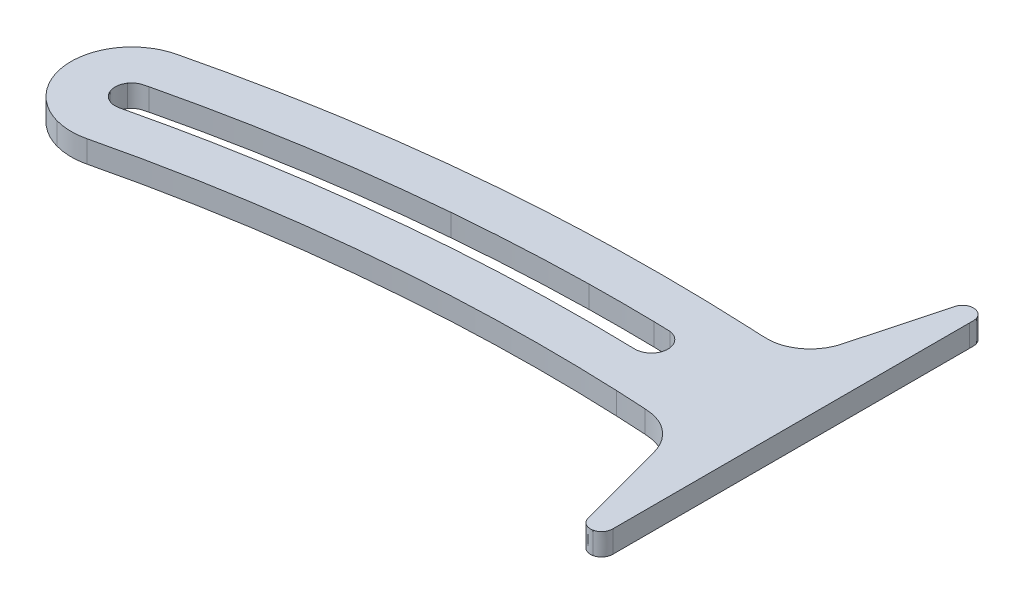
SolidWorks part; units mm, degrees
ref_plane "Front Plane" through (0, 0, 0) normal (0, 0, 1) x (1, 0, 0)
ref_plane "Top Plane" through (0, 0, 0) normal (0, 1, 0) x (1, 0, 0)
ref_plane "Right Plane" through (0, 0, 0) normal (1, 0, 0) x (0, 0, -1)
sketch "Imported Profile" plane through (0, 0, 0) normal (0, 1, 0) x (1, 0, 0)
  spline S0 degree 3 poles (12.8991, 25.236) (15.9171, 24.4093) (18.7007, 24.3473) (21.7531, 25.0501) knots 0 0 0 0 1 1 1 1
  spline S1 degree 3 poles (21.7531, 25.0501) (67.2422, 35.9573) (114.0335, 40.4773) (160.7696, 38.4929) knots 0 0 0 0 1 1 1 1
  spline S2 degree 3 poles (160.7696, 38.4929) (163.6635, 38.3689) (166.5574, 38.2174) (169.4444, 38.0449) knots 0 0 0 0 1 1 1 1
  spline S3 degree 3 poles (169.4444, 38.0449) (172.5863, 37.8589) (175.1081, 37.0734) (177.5541, 34.9719) knots 0 0 0 0 1 1 1 1
  spline S4 degree 3 poles (177.5541, 34.9719) (178.7254, 33.9728) (179.6419, 32.8428) (180.3929, 31.4993) knots 0 0 0 0 1 1 1 1
  spline S5 degree 3 poles (180.3929, 31.4993) (181.1026, 30.2177) (181.4953, 28.8603) (181.8674, 27.4685) knots 0 0 0 0 1 1 1 1
  spline S6 degree 3 poles (181.8674, 27.4685) (182.6184, 24.6642) (183.3694, 21.8599) (184.1205, 19.0625) knots 0 0 0 0 1 1 1 1
  spline S7 degree 3 poles (184.1205, 19.0625) (184.8715, 16.2582) (185.6225, 13.4539) (186.3735, 10.6495) knots 0 0 0 0 1 1 1 1
  spline S8 degree 3 poles (186.3735, 10.6495) (186.7457, 9.2508) (187.1246, 7.8521) (187.4967, 6.4465) knots 0 0 0 0 1 1 1 1
  spline S9 degree 3 poles (187.4967, 6.4465) (187.6827, 5.7506) (187.8756, 5.0478) (188.0617, 4.345) knots 0 0 0 0 1 1 1 1
  spline S10 degree 3 poles (188.0617, 4.345) (188.2477, 3.6491) (188.3786, 2.9463) (188.6335, 2.2642) knots 0 0 0 0 1 1 1 1
  spline S11 degree 3 poles (188.6335, 2.2642) (189.1847, 0.8172) (190.7006, -0.0165) (192.2233, 0.2798) knots 0 0 0 0 1 1 1 1
  spline S12 degree 3 poles (192.2233, 0.2798) (193.7874, 0.5968) (194.7796, 1.9335) (194.7796, 3.4975) knots 0 0 0 0 1 1 1 1
  spline S13 degree 3 poles (194.7796, 3.4975) (194.7796, 6.3983) (194.7796, 9.2991) (194.7796, 12.1998) knots 0 0 0 0 1 1 1 1
  spline S14 degree 3 poles (194.7796, 12.1998) (194.7796, 35.5507) (194.7796, 58.9084) (194.7796, 82.2593) knots 0 0 0 0 1 1 1 1
  spline S15 degree 3 poles (194.7796, 82.2593) (194.7796, 88.0608) (194.7796, 93.8624) (194.7796, 99.6708) knots 0 0 0 0 1 1 1 1
  spline S16 degree 3 poles (194.7796, 99.6708) (194.7796, 101.1178) (194.7796, 102.5716) (194.7796, 104.0185) knots 0 0 0 0 1 1 1 1
  spline S17 degree 3 poles (194.7796, 104.0185) (194.7796, 104.742) (194.7796, 105.4724) (194.7796, 106.1958) knots 0 0 0 0 1 1 1 1
  spline S18 degree 3 poles (194.7796, 106.1958) (194.7796, 106.9193) (194.8485, 107.6152) (194.6072, 108.3387) knots 0 0 0 0 1 1 1 1
  spline S19 degree 3 poles (194.6072, 108.3387) (194.1043, 109.7994) (192.6229, 110.6882) (191.0932, 110.4402) knots 0 0 0 0 1 1 1 1
  spline S20 degree 3 poles (191.0932, 110.4402) (190.2595, 110.3027) (189.6807, 109.9717) (189.1433, 109.3171) knots 0 0 0 0 1 1 1 1
  spline S21 degree 3 poles (189.1433, 109.3171) (188.6541, 108.7176) (188.5094, 108.0424) (188.3234, 107.3327) knots 0 0 0 0 1 1 1 1
  spline S22 degree 3 poles (188.3234, 107.3327) (186.8213, 101.731) (185.3193, 96.1292) (183.8172, 90.5206) knots 0 0 0 0 1 1 1 1
  spline S23 degree 3 poles (183.8172, 90.5206) (183.0662, 87.7232) (182.3909, 84.912) (181.5641, 82.1353) knots 0 0 0 0 1 1 1 1
  spline S24 degree 3 poles (181.5641, 82.1353) (180.7097, 79.2483) (178.8563, 76.7678) (176.3413, 75.121) knots 0 0 0 0 1 1 1 1
  spline S25 degree 3 poles (176.3413, 75.121) (172.2486, 72.4477) (169.1411, 73.0678) (164.7796, 73.2676) knots 0 0 0 0 1 1 1 1
  spline S26 degree 3 poles (164.7796, 73.2676) (145.3906, 74.1909) (126.0843, 74.1289) (106.7022, 73.0126) knots 0 0 0 0 1 1 1 1
  spline S27 degree 3 poles (106.7022, 73.0126) (83.2893, 71.6621) (60.2485, 68.6924) (37.2422, 64.1724) knots 0 0 0 0 1 1 1 1
  spline S28 degree 3 poles (37.2422, 64.1724) (29.3115, 62.6153) (21.4154, 60.9065) (13.5537, 58.9979) knots 0 0 0 0 1 1 1 1
  spline S29 degree 3 poles (13.5537, 58.9979) (13.4434, 58.9679) (13.3332, 58.9429) (13.2298, 58.9154) knots 0 0 0 0 1 1 1 1
  spline S30 degree 3 poles (13.2298, 58.9154) (13.0093, 58.8604) (12.7889, 58.7984) (12.5753, 58.7294) knots 0 0 0 0 1 1 1 1
  spline S31 degree 3 poles (12.5753, 58.7294) (12.1274, 58.5914) (11.6933, 58.4469) (11.2661, 58.2744) knots 0 0 0 0 1 1 1 1
  spline S32 degree 3 poles (11.2661, 58.2744) (10.3773, 57.9229) (9.5298, 57.5027) (8.7099, 57.0135) knots 0 0 0 0 1 1 1 1
  spline S33 degree 3 poles (8.7099, 57.0135) (6.9735, 55.9731) (5.5197, 54.726) (4.2313, 53.1688) knots 0 0 0 0 1 1 1 1
  spline S34 degree 3 poles (4.2313, 53.1688) (1.7439, 50.1716) (0.3383, 46.4302) (0.2281, 42.5373) knots 0 0 0 0 1 1 1 1
  spline S35 degree 3 poles (0.2281, 42.5373) (-0.0062, 34.5515) (5.2166, 27.4271) (12.8991, 25.236) knots 0 0 0 0 1 1 1 1
  spline S36 degree 3 poles (153.0044, 51.4685) (156.4908, 51.3706) (158.8886, 54.9191) (157.5036, 58.1161) knots 0 0 0 0 1 1 1 1
  spline S37 degree 3 poles (157.5036, 58.1161) (156.8353, 59.6595) (155.409, 60.7344) (153.7416, 60.948) knots 0 0 0 0 1 1 1 1
  spline S38 degree 3 poles (153.7416, 60.948) (153.2937, 61.01) (149.5386, 61.072) (149.0907, 61.079) knots 0 0 0 0 1 1 1 1
  spline S39 degree 3 poles (149.0907, 61.079) (142.8482, 61.196) (136.5988, 61.203) (130.3494, 61.094) knots 0 0 0 0 1 1 1 1
  spline S40 degree 3 poles (130.3494, 61.094) (117.7059, 60.8805) (105.1106, 60.212) (92.5154, 59.0889) knots 0 0 0 0 1 1 1 1
  spline S41 degree 3 poles (92.5154, 59.0889) (67.2422, 56.8358) (42.4581, 52.8051) (17.7706, 46.9484) knots 0 0 0 0 1 1 1 1
  spline S42 degree 3 poles (17.7706, 46.9484) (16.1652, 46.5694) (14.7734, 46.2387) (13.7329, 44.6953) knots 0 0 0 0 1 1 1 1
  spline S43 degree 3 poles (13.7329, 44.6953) (12.8234, 43.3517) (12.6649, 41.6499) (13.3057, 40.1547) knots 0 0 0 0 1 1 1 1
  spline S44 degree 3 poles (13.3057, 40.1547) (13.9672, 38.6044) (15.4072, 37.5226) (17.0816, 37.309) knots 0 0 0 0 1 1 1 1
  spline S45 degree 3 poles (17.0816, 37.309) (17.8808, 37.2055) (18.6112, 37.359) (19.3691, 37.5365) knots 0 0 0 0 1 1 1 1
  spline S46 degree 3 poles (19.3691, 37.5365) (20.127, 37.7225) (20.8849, 37.9015) (21.6429, 38.074) knots 0 0 0 0 1 1 1 1
  spline S47 degree 3 poles (21.6429, 38.074) (27.7269, 39.5002) (33.8316, 40.8094) (39.9708, 42.0151) knots 0 0 0 0 1 1 1 1
  spline S48 degree 3 poles (39.9708, 42.0151) (52.38, 44.4405) (64.8375, 46.4111) (77.3914, 47.9269) knots 0 0 0 0 1 1 1 1
  spline S49 degree 3 poles (77.3914, 47.9269) (102.5751, 50.9655) (127.6485, 52.1368) (153.0044, 51.4685) knots 0 0 0 0 1 1 1 1
extrude "Boss-Extrude1" add sketch "Imported Profile" along normal blind 6.35
sketch "Sketch1" plane through (0, 6.35, 0) normal (0, 1, 0) x (1, 0, 0)
  line L0 (191.616, 107.3087) -> (191.616, 3.4975) construction
  line L1 (194.7796, 107.3087) -> (194.7796, 3.4975) construction
  line L2 (188.4524, 107.3087) -> (188.4524, 3.4975) construction
  line L5 (194.7796, 12.1998) -> (194.7796, 82.2593) construction
  line L6 (194.7796, 55.4031) -> (171.9196, 55.4031) construction
  arc A0 (194.7796, 107.3087) -> (188.4524, 107.3087) centre (191.616, 107.3087) ccw construction
  arc A1 (188.4524, 3.4975) -> (194.7796, 3.4975) centre (191.616, 3.4975) ccw construction
  spline S0 degree 3 poles (194.6072, 108.3387) (194.1043, 109.7994) (192.6229, 110.6882) (191.0932, 110.4402) knots 0 0 0 0 1 1 1 1 construction
  spline S1 degree 3 poles (192.2233, 0.2798) (193.7874, 0.5968) (194.7796, 1.9335) (194.7796, 3.4975) knots 0 0 0 0 1 1 1 1 construction
  point P2 (191.616, 55.4031)
  dimension "D1" = 22.86
  dimension "D2" = 6.3272
sketch3d "3DSketch1"
  line L0 (171.9196, 6.35, -55.4031) -> (171.9196, 0, -55.4031) construction
sketch "Sketch2" plane through (0, 0, 0) normal (0, -1, 0) x (1, 0, 0)
  line L0 (131.3895, -51.8859) -> (96.6153, -50.1813) construction
  line L1 (114.0024, -51.0336) -> (113.5363, -60.5407) construction
  line L2 (41.428, -42.497) -> (69.6198, -47.1272) construction
  line L3 (55.5239, -44.8121) -> (53.9795, -54.2158) construction
  circle A0 centre (153.1375, -56.2248) radius 4.7582 construction
  circle A1 centre (17.6798, -42.0304) radius 4.7593 construction
  spline S0 degree 3 poles (153.0044, -51.4685) (156.4908, -51.3706) (158.8886, -54.9191) (157.5036, -58.1161) knots 0 0 0 0 1 1 1 1 construction
  spline S2 degree 3 poles (17.0816, -37.309) (17.8808, -37.2055) (18.6112, -37.359) (19.3691, -37.5365) knots 0 0 0 0 1 1 1 1 construction
  spline S3 degree 3 poles (13.7329, -44.6953) (12.8234, -43.3517) (12.6649, -41.6499) (13.3057, -40.1547) knots 0 0 0 0 1 1 1 1 construction
  spline S4 degree 3 poles (153.1375, -56.2248) (107.1548, -57.4301) (62.0117, -52.6466) (17.6798, -42.0304) knots 0 0 0 0 1 1 1 1
  spline S7 degree 3 poles (77.3914, -47.9269) (102.5751, -50.9655) (127.6485, -52.1368) (153.0044, -51.4685) knots 0 0 0 0 1 1 1 1 construction
  spline S8 degree 3 poles (130.3494, -61.094) (117.7059, -60.8805) (105.1106, -60.212) (92.5154, -59.0889) knots 0 0 0 0 1 1 1 1 construction
  spline S10 degree 3 poles (92.5154, -59.0889) (67.2422, -56.8358) (42.4581, -52.8051) (17.7706, -46.9484) knots 0 0 0 0 1 1 1 1 construction
  spline S11 degree 3 poles (39.9708, -42.0151) (52.38, -44.4405) (64.8375, -46.4111) (77.3914, -47.9269) knots 0 0 0 0 1 1 1 1 construction
  point P16 (114.0024, -51.0336)
  point P18 (113.7694, -55.7872)
  point P26 (55.5239, -44.8121)
  point P38 (54.7517, -49.5139)
  dimension "D1" = 39.002
  dimension "D2" = 33.8811
